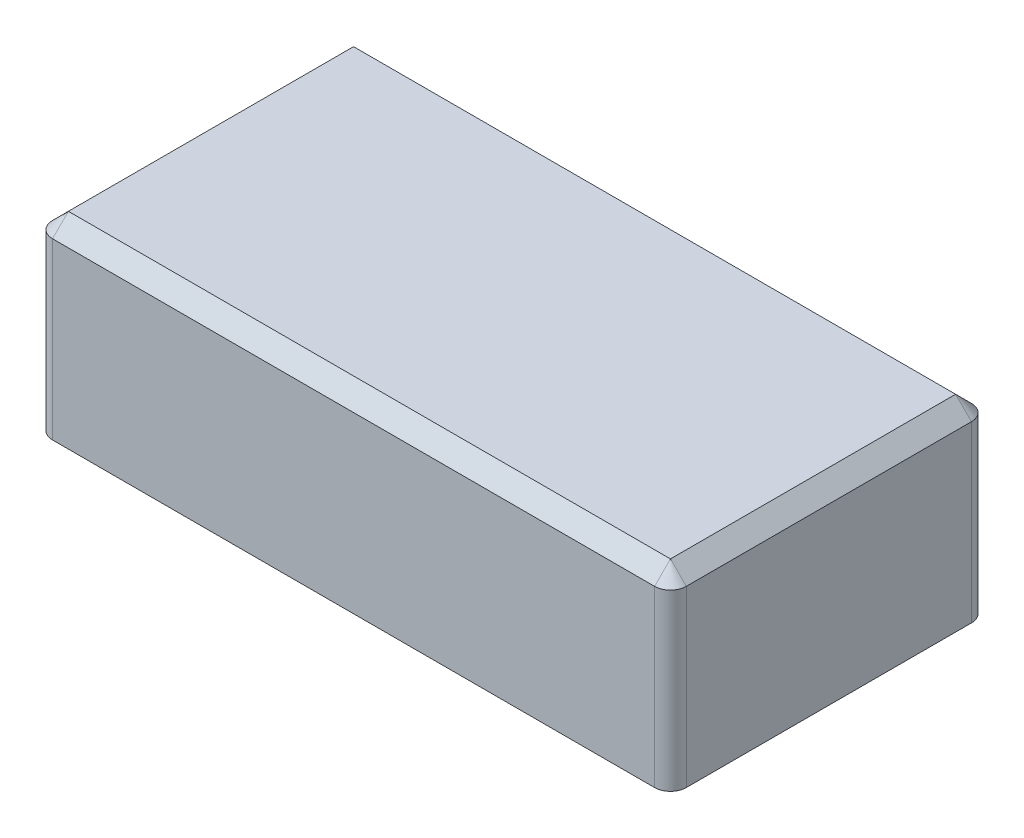
SolidWorks part; units mm, degrees
material "Beton"
ref_plane "Płaszczyzna przednia" through (0, 0, 0) normal (0, 0, 1) x (1, 0, 0)
ref_plane "Płaszczyzna górna" through (0, 0, 0) normal (0, 1, 0) x (1, 0, 0)
ref_plane "Płaszczyzna prawa" through (0, 0, 0) normal (1, 0, 0) x (0, 0, -1)
sketch3d "Szkic 3D1"
  line L0 (0, 0, 0) -> (200, 0, 0)
  line L1 (200, 0, 0) -> (200, 60, 0)
  line L2 (200, 60, 0) -> (0, 60, 0)
  line L3 (0, 60, 0) -> (0, 0, 0)
  dimension "D1" = 60
  dimension "D2" = 200
extrude "Dodanie-wyciągnięcie1" add sketch "Szkic 3D1" along direction (0, 0, 1) on the side against the normal blind 100 contours L0 L1 L2 L3
fillet "Zaokrąglenie4" radius 5 4 edges
fillet "Zaokrąglenie5" radius 5 8 edges at (198.5355, 60, 98.5355) (1.4645, 60, 98.5355) (1.4645, 60, 1.4645) (198.5355, 60, 1.4645)
